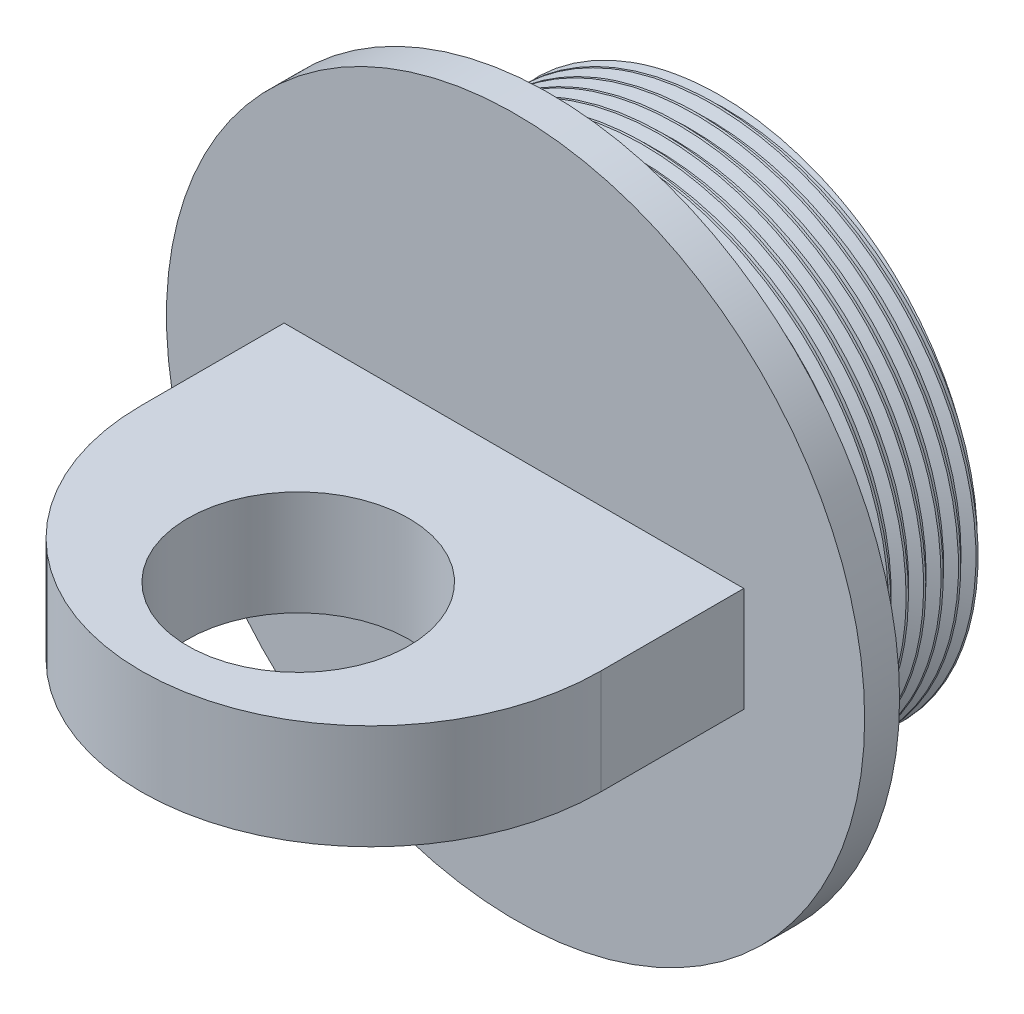
SolidWorks part; units mm, degrees
ref_plane "Front Plane" through (0, 0, 0) normal (1, 0, 0) x (0, 1, 0)
ref_plane "Top Plane" through (0, 0, 0) normal (0, 0, 1) x (0, 1, 0)
ref_plane "Right Plane" through (0, 0, 0) normal (0, 1, 0) x (-1, 0, 0)
sketch "Sketch2" plane through (0, 0, 0) normal (0, 0, 1) x (0, 1, 0)
  circle A0 centre (0, 0) radius 25.4
  dimension "D1" = 50.8
extrude "Boss-Extrude1" add sketch "Sketch2" along normal blind 2.54
sketch "Sketch4" plane through (0, 0, 0) normal (0, 1, 0) x (-1, 0, 0)
  line L1 (-16.605, 2.54) -> (-16.605, 12.9379)
  line L2 (25.4, 2.54) -> (-25.4, 2.54) construction
  line L3 (16.8384, 2.54) -> (-16.605, 2.54)
  line L4 (16.8384, 12.9379) -> (16.8384, 2.54)
  arc A0 (-16.605, 12.9379) -> (16.8384, 12.9379) centre (0.1167, 12.9379) cw
extrude "Boss-Extrude2" add sketch "Sketch4" along normal mid plane 7.62 contours A0 L4 L3 L1
sketch "Sketch5" plane through (0, 3.81, 0) normal (0, 1, 0) x (-1, 0, 0)
  circle A0 centre (0, 18.3523) radius 8.0443
extrude "Cut-Extrude1" cut sketch "Sketch5" against normal through all both and the other way through all
sketch "Sketch6" plane through (0, 0, 0) normal (0, 0, -1) x (1, 0, 0)
  circle A0 centre (0, 0) radius 19.05
  dimension "D1" = 38.1
extrude "Boss-Extrude3" add sketch "Sketch6" along normal blind 12.7
thread "Thread1" pitch 1.27 method cut profile "Thread Profile1" start angle 0, offset 0, length 12.7, pitch 1.27, diameter 38.1
ref_plane "Plane1" through (-19.05, 0, 0) normal (0, -1, 0) x (-1, 0, 0)
sketch "Thread Profile1" plane through (-19.05, 0, 0) normal (0, -1, 0) x (-1, 0, 0)
  line L0 (0, 0) -> (0, 1.27) construction
  line L11 (0, 0) -> (0, 1.1112)
  line L12 (0, 1.1112) -> (-0.6874, 0.7144)
  line L13 (-0.6874, 0.7144) -> (-0.6874, 0.3969)
  line L15 (-0.6874, 0.3969) -> (0, 0)
  line L17 (-0.6874, 0.5556) -> (0, 0.5556) construction
  point P2 (0, 0)
  dimension "Pitch" = 1.27
  dimension "Profile_Angle" = 60
  dimension "Profile_Land" = 0.3175
  dimension "Profile_Height" = 0.6874
